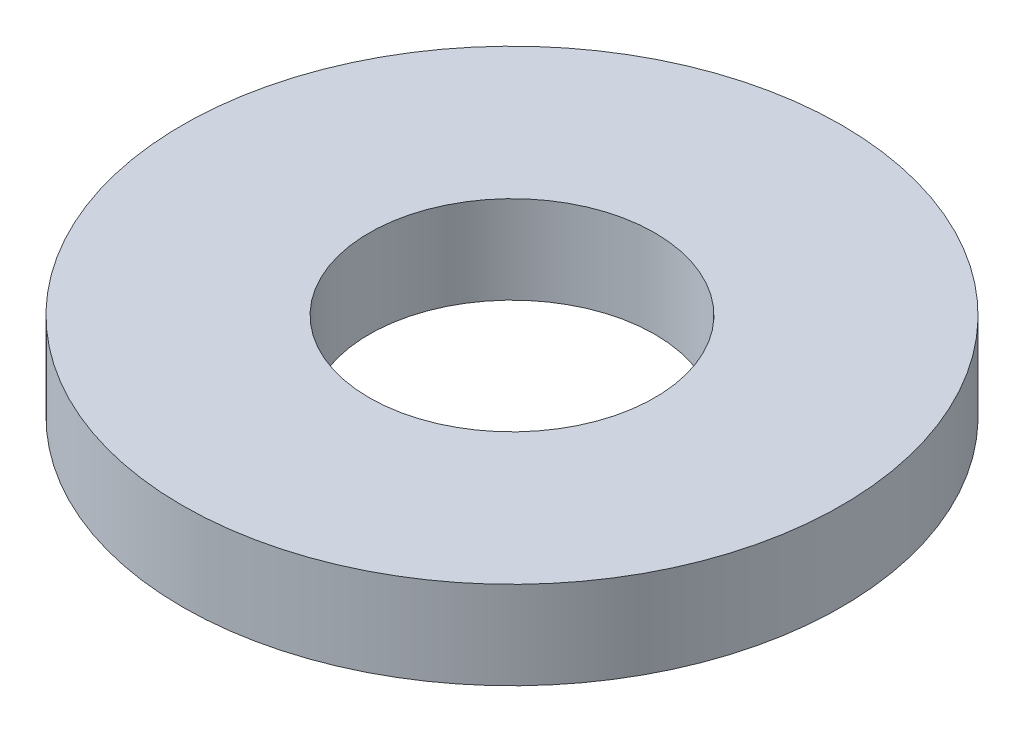
SolidWorks part; units mm, degrees
ref_plane "Front Plane" through (0, 0, 0) normal (0, 0, 1) x (1, 0, 0)
ref_plane "Top Plane" through (0, 0, 0) normal (0, 1, 0) x (1, 0, 0)
ref_plane "Right Plane" through (0, 0, 0) normal (1, 0, 0) x (0, 0, -1)
sketch "Sketch1" plane through (0, 0, 0) normal (0, 1, 0) x (1, 0, 0)
  circle A0 centre (0, 0) radius 75
  dimension "FLANGE_OD" = 150
extrude "Boss-Extrude1" add sketch "Sketch1" along normal blind 20
sketch "Sketch2" plane through (0, 0, 0) normal (0, 1, 0) x (1, 0, 0)
  circle A0 centre (0, 0) radius 32.5
  dimension "BORE_D" = 65
extrude "Cut-Extrude1" cut sketch "Sketch2" along normal through all
sketch "Sketch3" plane through (0, 20, 0) normal (0, 1, 0) x (1, 0, 0)
  circle A0 centre (0, 0) radius 19.259 construction
  circle A1 centre (-19.259, 0) radius 4.954
  dimension "BOLT_D" = 9.908
  dimension "BOLT_PCD" = 38.518
extrude "Cut-Extrude2" cut sketch "Sketch3" against normal blind 19.0935 rebuild error yes
pattern_circular "CirPattern1" count 6 over 360 rebuild error yes
